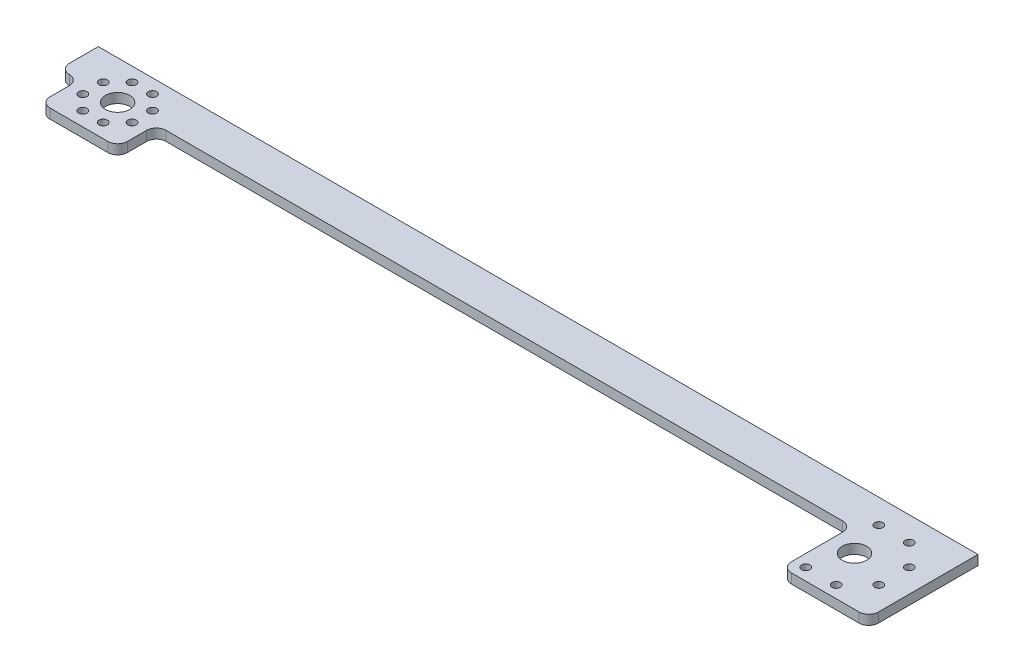
SolidWorks part; units mm, degrees
ref_plane "Front Plane" through (0, 0, 0) normal (0, 0, 1) x (1, 0, 0)
ref_plane "Top Plane" through (0, 0, 0) normal (0, 1, 0) x (1, 0, 0)
ref_plane "Right Plane" through (0, 0, 0) normal (1, 0, 0) x (0, 0, -1)
sketch "Sketch1" plane through (0, 0, 0) normal (0, 1, 0) x (1, 0, 0)
  line L1 (-228.6, 12.7) -> (228.6, 12.7)
  line L2 (-228.6, 12.7) -> (-228.6, -12.7) construction
  line L3 (-228.6, -12.7) -> (228.6, -12.7)
  line L4 (228.6, 12.7) -> (228.6, -12.7) construction
  line L5 (-228.6, 12.7) -> (228.6, -12.7) construction
  line L6 (-228.6, -12.7) -> (228.6, 12.7) construction
  line L7 (-228.6, 12.7) -> (-279.4, 12.7)
  line L8 (-279.4, 12.7) -> (-279.4, -38.1) construction
  line L9 (-279.4, -38.1) -> (-228.6, -38.1)
  line L10 (-228.6, -38.1) -> (-228.6, -12.7)
  line L11 (-279.4, 12.7) -> (-292.1, 12.7)
  line L12 (-292.1, 12.7) -> (-292.1, -12.7)
  line L13 (-292.1, -12.7) -> (-279.4, -12.7)
  line L14 (-279.4, -12.7) -> (-279.4, -38.1)
  line L15 (228.6, 12.7) -> (285.75, 12.7)
  line L16 (285.75, 12.7) -> (285.75, -59.055)
  line L17 (285.75, -59.055) -> (228.6, -59.055)
  line L18 (228.6, -59.055) -> (228.6, -12.7)
  point P0 (0, 0)
  dimension "D1" = 25.4
  dimension "D2" = 457.2
  dimension "D3" = 50.8
  dimension "D4" = 50.8
  dimension "D5" = 12.7
  dimension "D6" = 57.15
  dimension "D7" = 46.355
extrude "Boss-Extrude1" add sketch "Sketch1" along normal blind 6.35 contours L1 L15 L16 L17 L18 L3 L10 L9 L14 L13 L12 L11 L7
hole_wizard "M5 Clearance Hole1" positions "Sketch2" profile "Sketch3" hole size "M5" standard "ANSI Metric"
sketch "Sketch2" plane through (0, 6.35, 0) normal (0, 1, 0) x (1, 0, 0)
  line L0 (-279.4, -38.1) -> (-228.6, -38.1) construction
  line L15 (-270.1679, -19.397) -> (-270.1679, -6.003) construction
  line L16 (-270.1679, -6.003) -> (-260.697, 3.4679) construction
  line L17 (-260.697, 3.4679) -> (-247.303, 3.4679) construction
  line L18 (-247.303, 3.4679) -> (-237.8321, -6.003) construction
  line L19 (-237.8321, -6.003) -> (-237.8321, -19.397) construction
  line L20 (-237.8321, -19.397) -> (-247.303, -28.8679) construction
  line L21 (-247.303, -28.8679) -> (-260.697, -28.8679) construction
  line L22 (-260.697, -28.8679) -> (-270.1679, -19.397) construction
  circle A0 centre (-254, -12.7) radius 17.5 construction
  point P23 (-254, -38.1)
  point P37 (-260.697, -28.8679)
  point P41 (-237.8321, -19.397)
  point P67 (-260.697, 3.4679)
  point P69 (-247.303, 3.4679)
  point P71 (-237.8321, -6.003)
  point P84 (-270.1679, -19.397)
  point P107 (-247.303, -28.8679)
  point P110 (-270.1679, -6.003)
  dimension "D1" = 35
  dimension "D2" = 135
  dimension "D3" = 135
  dimension "D4" = 135
  dimension "D5" = 135
  dimension "D6" = 135
  dimension "D7" = 135
sketch "Sketch3" plane through (-270.1679, 6.35, 6.003) normal (1, 0, 0) x (0, 0, 1)
  line L0 (0, 0) -> (0, 14.3524)
  line L1 (0, 14.3524) -> (2.75, 12.7)
  line L2 (2.75, 12.7) -> (2.75, 0)
  line L5 (2.75, 0) -> (0, 0)
  line L10 (0, 14.3524) -> (-2.75, 12.7) construction
  line L11 (0, -6.35) -> (0, 107.95) construction
  dimension "Hole Dia." = 5.5
  dimension "Hole Depth" = 12.7
  dimension "Drill Angle" = 118
hole_wizard "#6 Clearance Hole2" positions "Sketch6" profile "Sketch7" hole size "#6" standard "ANSI Inch"
sketch "Sketch6" plane through (0, 0, -12.7) normal (0, 0, -1) x (-1, 0, 0)
  line L0 (215.9, 3.175) -> (-215.9, 3.175) construction
  line L2 (292.1, 0) -> (-285.75, 0) construction
  line L4 (292.1, 6.35) -> (292.1, 0) construction
  line L5 (-228.6, 6.35) -> (-228.6, 0) construction
  line L6 (-285.75, 6.35) -> (-285.75, 0) construction
  point P0 (279.4, 3.175)
  point P2 (215.9, 3.175)
  point P4 (0, 3.175)
  point P6 (-215.9, 3.175)
  point P14 (0, 3.175)
  point P26 (-276.225, 3.175)
  dimension "D1" = 3.175
  dimension "D2" = 12.7
  dimension "D3" = 12.7
  dimension "D4" = 12.7
  dimension "D5" = 9.525
sketch "Sketch7" plane through (-279.4, 3.175, -12.7) normal (1, 0, 0) x (0, 1, 0)
  line L0 (0, 0) -> (0, 13.8408)
  line L1 (0, 13.8408) -> (1.8986, 12.7)
  line L2 (1.8986, 12.7) -> (1.8986, 0)
  line L5 (1.8986, 0) -> (0, 0)
  line L10 (0, 13.8408) -> (-1.8986, 12.7) construction
  line L11 (0, -6.35) -> (0, 107.95) construction
  dimension "Hole Dia." = 3.7973
  dimension "Hole Depth" = 12.7
  dimension "Drill Angle" = 118
hole_wizard "M5 Clearance Hole2" positions "Sketch9" profile "Sketch10" hole size "M5" standard "ANSI Metric"
sketch "Sketch9" plane through (0, 6.35, 0) normal (0, 1, 0) x (1, 0, 0)
  line L1 (218.475, -17.175) -> (218.475, -37.175) construction
  line L3 (285.75, 12.7) -> (-292.1, 12.7) construction
  line L6 (228.6, -59.055) -> (228.6, -12.7) construction
  point P0 (218.475, -17.175)
  point P3 (218.475, -37.175)
  point P16 (244.475, -27.175)
  point P20 (256.475, -3.175)
  point P22 (256.475, -51.175)
  point P26 (236.475, -3.175)
  point P28 (236.475, -51.175)
  point P40 (218.475, -27.175)
  point P48 (270.475, -17.175)
  point P50 (270.475, -37.175)
  dimension "D1" = 15.875
  dimension "D2" = 20
  dimension "D3" = 15.875
  dimension "D4" = 26
  dimension "D5" = 8
  dimension "D6" = 24
  dimension "D7" = 48
  dimension "D8" = 20
  dimension "D9" = 26
sketch "Sketch10" plane through (218.475, 6.35, 17.175) normal (1, 0, 0) x (0, 0, 1)
  line L0 (0, 0) -> (0, 14.3524)
  line L1 (0, 14.3524) -> (2.75, 12.7)
  line L2 (2.75, 12.7) -> (2.75, 0)
  line L5 (2.75, 0) -> (0, 0)
  line L10 (0, 14.3524) -> (-2.75, 12.7) construction
  line L11 (0, -6.35) -> (0, 107.95) construction
  dimension "Hole Dia." = 5.5
  dimension "Hole Depth" = 12.7
  dimension "Drill Angle" = 118
fillet "Fillet1" radius 6.35 8 edges at (-228.6, 3.175, 38.1) (-228.6, 3.175, 12.7) (-292.1, 3.175, 12.7) (-279.4, 3.175, 38.1) (-279.4, 3.175, 12.7) (285.75, 3.175, 59.055) (228.6, 3.175, 59.055) (228.6, 3.175, 12.7)
sketch "Sketch8" plane through (0, 6.35, 0) normal (0, 1, 0) x (1, 0, 0)
  circle A0 centre (-254, -12.7) radius 8
  circle A1 centre (244.475, -27.175) radius 8
  dimension "D1" = 16
  dimension "D2" = 16
extrude "Cut-Extrude1" cut sketch "Sketch8" against normal blind 6.35
